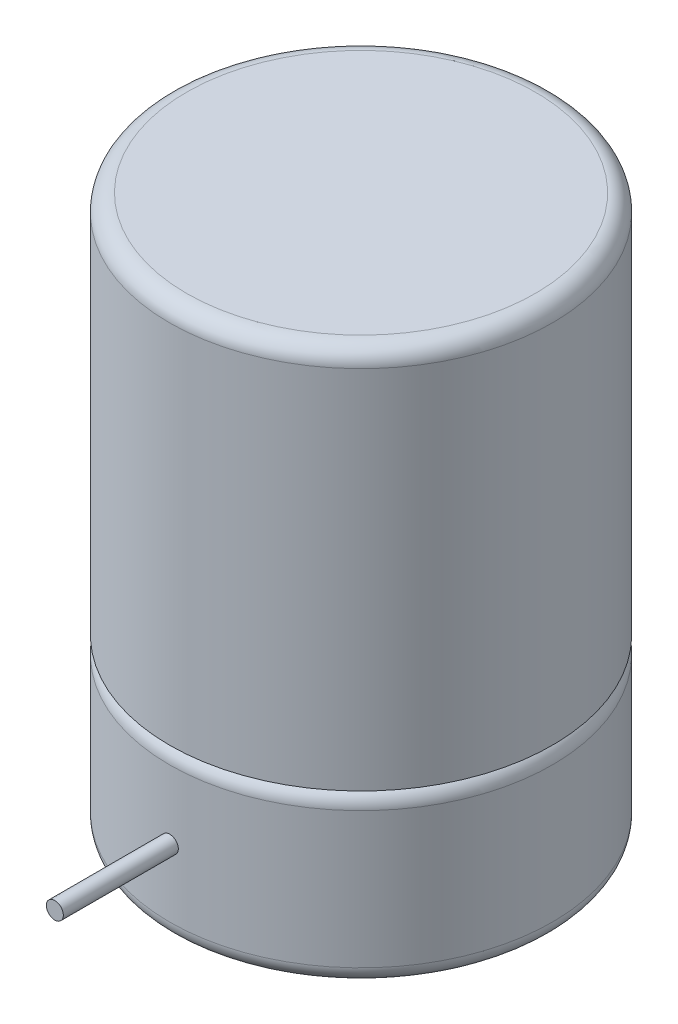
SolidWorks part; units mm, degrees
ref_plane "Front Plane" through (0, 0, 0) normal (0, 0, 1) x (1, 0, 0)
ref_plane "Top Plane" through (0, 0, 0) normal (0, 1, 0) x (1, 0, 0)
ref_plane "Right Plane" through (0, 0, 0) normal (1, 0, 0) x (0, 0, -1)
sketch "Sketch1" plane through (0, 0, 0) normal (0, 1, 0) x (1, 0, 0)
  circle A0 centre (0, 0) radius 14.2875
  dimension "D1" = 28.575
extrude "Boss-Extrude1" add sketch "Sketch1" along normal blind 12.7
fillet "Fillet1" radius 1.27 2 edges at (0, 0, 14.2875) (0, 12.7, 14.2875)
sketch "Sketch3" plane through (0, 12.7, 0) normal (0, 1, 0) x (1, 0, 0)
  circle A0 centre (0, 0) radius 14.2875
extrude "Boss-Extrude2" add sketch "Sketch3" along normal blind 28.575
fillet "Fillet2" radius 1.27 1 edges at (0, 41.275, 14.2875)
sketch "Sketch4" plane through (0, 0, 0) normal (0, 0, 1) x (1, 0, 0)
  circle A0 centre (0, 6.3189) radius 0.635
  dimension "D1" = 1.27
extrude "Boss-Extrude3" add sketch "Sketch4" along normal blind 22.86
